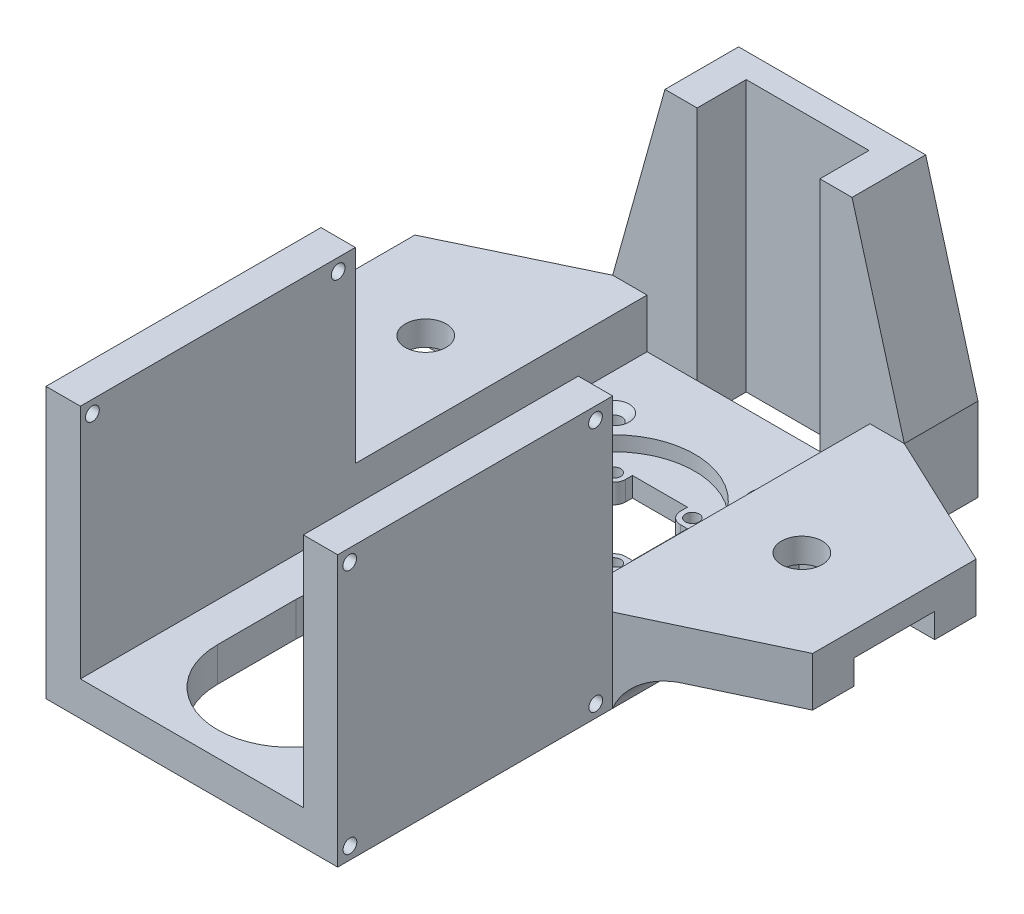
SolidWorks part; units mm, degrees
ref_plane "Front Plane" through (0, 0, 0) normal (0, 0, 1) x (1, 0, 0)
ref_plane "Top Plane" through (0, 0, 0) normal (0, 1, 0) x (1, 0, 0)
ref_plane "Right Plane" through (0, 0, 0) normal (1, 0, 0) x (0, 0, -1)
sketch "Sketch1" plane through (0, 0, 0) normal (0, 1, 0) x (1, 0, 0)
  line L1 (-29.9233, 15.7991) -> (29.4767, 15.7991)
  line L2 (-29.9233, 15.7991) -> (-29.9233, -43.6009)
  line L3 (-29.9233, -43.6009) -> (29.4767, -43.6009)
  line L4 (29.4767, 15.7991) -> (29.4767, -43.6009)
  dimension "D1" = 59.4
  dimension "D2" = 59.4
extrude "Boss-Extrude1" add sketch "Sketch1" along normal blind 7
sketch "Sketch2" plane through (0, 7, 0) normal (0, 1, 0) x (1, 0, 0)
  circle A0 centre (0, -13.9009) radius 16.5
  dimension "D1" = 33
extrude "Cut-Extrude1" cut sketch "Sketch2" against normal blind 3
sketch "Sketch4" plane through (0, 7, 0) normal (0, 1, 0) x (1, 0, 0)
  circle A1 centre (0, -13.9009) radius 16.5 construction
  circle A5 centre (-15.5, 1.5991) radius 1.65
  circle A6 centre (0, -13.9009) radius 16.5 construction
  circle A7 centre (15.5, 1.5991) radius 1.65
  circle A8 centre (15.5, -29.4009) radius 1.65
  circle A9 centre (-15.5, -29.4009) radius 1.65
  point P13 (0, -13.9009)
  point P24 (0, -13.9009)
  dimension "D4" = 15.5
  dimension "D5" = 15.5
  dimension "D6" = 3.3
  dimension "D7" = 4
extrude "Cut-Extrude2" cut sketch "Sketch4" against normal blind 7
chamfer "Chamfer1" distance 1.5 angle 45 4 edges at (-15.5, 7, 31.0509) (15.5, 7, 31.0509) (15.5, 7, 0.0509) (-15.5, 7, 0.0509)
sketch "Sketch5" plane through (0, 4, 0) normal (0, 1, 0) x (1, 0, 0)
  line L0 (-8, -8.3009) -> (-9.4, -8.3009)
  line L1 (-9.4, -8.3009) -> (-9.4, -13.9009)
  line L2 (-5.6, -5.9009) -> (-5.6, -4.5009)
  line L3 (-5.6, -4.5009) -> (0, -4.5009)
  line L4 (0, -4.5009) -> (0, -13.9009)
  line L5 (0, -13.9009) -> (-9.4, -13.9009)
  line L6 (0, -13.9009) -> (0, -4.5009)
  line L7 (9.4, -8.3009) -> (9.4, -13.9009)
  line L8 (8, -8.3009) -> (9.4, -8.3009)
  line L9 (5.6, -5.9009) -> (5.6, -4.5009)
  line L10 (5.6, -4.5009) -> (0, -4.5009)
  line L11 (9.4, -13.9009) -> (0, -13.9009)
  line L12 (0, -13.9009) -> (9.4, -13.9009)
  line L13 (5.6, -23.3009) -> (0, -23.3009)
  line L14 (5.6, -21.9009) -> (5.6, -23.3009)
  line L15 (8, -19.5009) -> (9.4, -19.5009)
  line L16 (9.4, -19.5009) -> (9.4, -13.9009)
  line L17 (0, -23.3009) -> (0, -13.9009)
  line L18 (0, -13.9009) -> (0, -23.3009)
  line L19 (-9.4, -19.5009) -> (-9.4, -13.9009)
  line L20 (-8, -19.5009) -> (-9.4, -19.5009)
  line L21 (-5.6, -21.9009) -> (-5.6, -23.3009)
  line L22 (-5.6, -23.3009) -> (0, -23.3009)
  line L23 (-9.4, -13.9009) -> (0, -13.9009)
  circle A0 centre (-8, -5.9009) radius 1.4
  circle A1 centre (0, -13.9009) radius 16.5 construction
  circle A2 centre (0, -13.9009) radius 16.5 construction
  circle A3 centre (-8, -5.9009) radius 2.4
  circle A4 centre (8, -5.9009) radius 2.4
  circle A5 centre (8, -5.9009) radius 1.4
  circle A6 centre (8, -21.9009) radius 2.4
  circle A7 centre (8, -21.9009) radius 1.4
  circle A8 centre (-8, -21.9009) radius 2.4
  circle A9 centre (-8, -21.9009) radius 1.4
  point P46 (0, -13.9009)
  dimension "D1" = 8
  dimension "D2" = 8
  dimension "D3" = 2.8
  dimension "D4" = 1
  dimension "D5" = 1.4
  dimension "D6" = 1.4
  dimension "D7" = 5.6
  dimension "D8" = 5.6
  dimension "D9" = 4
extrude "Cut-Extrude3" cut sketch "Sketch5" against normal blind 7 contours A6 L15 L16 L11 L17 L13 L14 | A8 L21 L22 L17 L5 L19 L20 | A3 L0 L1 L5 L4 L3 L2 | A4 L9 L10 L4 L11 L7 L8 | A5 | A0 | A9 | A7 region at (-4.1856, 4, 9.7153) region at (-4.1856, 4, 18.0866) region at (4.1856, 4, 9.7153) region at (4.1856, 4, 18.0866) region at (-8, 4, 5.9009) region at (8, 4, 5.9009) region at (8, 4, 21.9009) region at (-8, 4, 21.9009)
sketch "Sketch6" plane through (0, 7, 0) normal (0, 1, 0) x (1, 0, 0)
  line L0 (-29.9233, -43.6009) -> (29.4767, -43.6009) construction
  line L1 (-29.9233, 15.7991) -> (-22.9233, 15.7991)
  line L2 (-29.9233, 15.7991) -> (-29.9233, -43.6009)
  line L3 (-29.9233, -43.6009) -> (-22.9233, -43.6009)
  line L4 (-22.9233, 15.7991) -> (-22.9233, -43.6009)
  line L5 (29.4767, 15.7991) -> (-29.9233, 15.7991) construction
  line L6 (29.4767, -43.6009) -> (22.4767, -43.6009)
  line L7 (29.4767, -43.6009) -> (29.4767, 15.7991)
  line L8 (29.4767, 15.7991) -> (22.4767, 15.7991)
  line L9 (22.4767, -43.6009) -> (22.4767, 15.7991)
  dimension "D1" = 7
  dimension "D2" = 7
extrude "Boss-Extrude2" add sketch "Sketch6" along normal blind 10
sketch "Sketch7" plane through (0, 17, 0) normal (0, 1, 0) x (1, 0, 0)
  line L1 (-29.9233, 15.7991) -> (-57.15, 15.7991)
  line L2 (-29.9233, 15.7991) -> (-29.9233, -43.6009)
  line L3 (-29.9233, -43.6009) -> (-57.15, -43.6009)
  line L4 (-57.15, 15.7991) -> (-57.15, -43.6009)
  line L5 (29.4767, -43.6009) -> (57.15, -43.6009)
  line L6 (29.4767, -43.6009) -> (29.4767, 15.7991)
  line L7 (29.4767, 15.7991) -> (57.15, 15.7991)
  line L8 (57.15, -43.6009) -> (57.15, 15.7991)
  circle A0 centre (0, -13.9009) radius 16.5 construction
  dimension "D1" = 114.3
  dimension "D2" = 57.15
extrude "Boss-Extrude3" add sketch "Sketch7" against normal blind 10
sketch "Sketch8" plane through (0, 7, 0) normal (0, -1, 0) x (1, 0, 0)
  line L1 (-57.15, -15.7991) -> (-57.15, 43.6009) construction
  circle A0 centre (-38.3, 13.9009) radius 4.165
  circle A1 centre (38.3, 13.9009) radius 4.165
  dimension "D1" = 76.6
  dimension "D2" = 8.33
  dimension "D3" = 18.85
  dimension "D4" = 8.33
extrude "Cut-Extrude4" cut sketch "Sketch8" against normal blind 10
sketch "Sketch9" plane through (0, 7, 0) normal (0, -1, 0) x (1, 0, 0)
  line L0 (-29.9233, 43.6009) -> (-29.9233, -15.7991) construction
  line L1 (-59.9233, 22.1009) -> (-29.9233, 22.1009)
  line L2 (-59.9233, 22.1009) -> (-59.9233, 5.7009)
  line L3 (-59.9233, 5.7009) -> (-29.9233, 5.7009)
  line L4 (-29.9233, 22.1009) -> (-29.9233, 5.7009)
  line L5 (29.4767, 43.6009) -> (29.4767, -15.7991) construction
  line L6 (29.4767, 22.1009) -> (65.8683, 22.1009)
  line L7 (29.4767, 22.1009) -> (29.4767, 5.7009)
  line L8 (29.4767, 5.7009) -> (65.8683, 5.7009)
  line L9 (65.8683, 22.1009) -> (65.8683, 5.7009)
  circle A0 centre (-38.3, 13.9009) radius 4.165 construction
  dimension "D1" = 16.4
  dimension "D2" = 30
  dimension "D3" = 0
  dimension "D4" = 8.2
extrude "Cut-Extrude5" cut sketch "Sketch9" against normal blind 5
sketch "Sketch10" plane through (0, 7, 0) normal (0, -1, 0) x (1, 0, 0)
  line L0 (29.4767, 43.6009) -> (57.15, 30.5509)
  line L1 (57.15, 43.6009) -> (57.15, 22.1009) construction
  line L2 (57.15, 30.5509) -> (76.6251, 37.4902)
  line L3 (76.6251, 37.4902) -> (62.9409, 60.152)
  line L4 (62.9409, 60.152) -> (29.4767, 43.6009)
  line L5 (29.4767, -15.7991) -> (57.15, -2.7491)
  line L6 (57.15, 5.7009) -> (57.15, -15.7991) construction
  line L7 (57.15, -2.7491) -> (74.3098, -17.3284)
  line L8 (74.3098, -17.3284) -> (51.4239, -33.9039)
  line L9 (51.4239, -33.9039) -> (29.4767, -15.7991)
  line L12 (-29.9233, 43.6009) -> (-57.15, 30.5509)
  line L13 (-57.15, 22.1009) -> (-57.15, 43.6009) construction
  line L14 (-57.15, 30.5509) -> (-87.322, 42.7198)
  line L15 (-87.322, 42.7198) -> (-44.4169, 63.2847)
  line L16 (-44.4169, 63.2847) -> (-29.9233, 43.6009)
  line L17 (-29.9233, -15.7991) -> (-57.15, -2.7491)
  line L18 (-57.15, -15.7991) -> (-57.15, 5.7009) construction
  line L19 (-57.15, -2.7491) -> (-80.4324, -17.3313)
  line L20 (-80.4324, -17.3313) -> (-52.6315, -33.8276)
  line L21 (-52.6315, -33.8276) -> (-29.9233, -15.7991)
  circle A0 centre (38.3, 13.9009) radius 4.165 construction
  circle A1 centre (-38.3, 13.9009) radius 4.165 construction
  dimension "D1" = 33.3
  dimension "D2" = 16.65
  dimension "D3" = 33.3
  dimension "D4" = 16.65
extrude "Cut-Extrude6" cut sketch "Sketch10" against normal blind 10
sketch "Sketch11" plane through (0, 0, -15.7991) normal (0, 0, -1) x (-1, 0, 0)
  line L0 (-57.15, 17) -> (-29.4767, 17) construction
  line L1 (-29.4767, 0) -> (29.9233, 0)
  line L2 (-29.4767, 0) -> (-29.4767, 55.1)
  line L3 (-29.4767, 55.1) -> (29.9233, 55.1)
  line L4 (29.9233, 0) -> (29.9233, 55.1)
  line L5 (-29.4767, 17) -> (-18.8267, 55.1)
  line L6 (29.9233, 17) -> (19.2733, 55.1)
  line M3 (-22.4767, 17) -> (-29.4767, 17)
  line M4 (-29.4767, 17) -> (-29.4767, 7)
  line M5 (-29.4767, 7) -> (-29.4767, 0)
  line M6 (-29.4767, 0) -> (29.9233, 0)
  line M7 (29.9233, 0) -> (29.9233, 7)
  line M8 (29.9233, 7) -> (29.9233, 17)
  line M9 (29.9233, 17) -> (22.9233, 17)
  line M11 (22.9233, 17) -> (22.9233, 7)
  line M12 (22.9233, 7) -> (-22.4767, 7)
  line M13 (-22.4767, 7) -> (-22.4767, 17)
  dimension "D1" = 38.1
  dimension "D2" = 38.1
  dimension "D3" = 10.65
extrude "Boss-Extrude4" add sketch "Sketch11" along normal blind 15 contours L6 L3 L5 M9 M3 M13 M12 M11 | M3 M4 M5 M6 M7 M8 M9 M11 M12 M13 region at (-0.2233, 5.6411, -15.7991) region at (-0.2233, 30.2114, -15.7991)
sketch "Sketch12" plane through (0, 55.1, 0) normal (0, 1, 0) x (1, 0, 0)
  line L0 (18.8267, 15.7991) -> (-19.2733, 15.7991) construction
  line L1 (-12.7233, 15.7991) -> (12.2767, 15.7991)
  line L2 (-12.7233, 15.7991) -> (-12.7233, 25.7991)
  line L3 (-12.7233, 25.7991) -> (12.2767, 25.7991)
  line L4 (12.2767, 15.7991) -> (12.2767, 25.7991)
  line L6 (-19.2733, 30.7991) -> (-19.2733, 15.7991) construction
  dimension "D1" = 25
  dimension "D2" = 6.55
  dimension "D3" = 10
extrude "Cut-Extrude7" cut sketch "Sketch12" against normal blind 90
sketch "Sketch13" plane through (0, 0, 0) normal (0, -1, 0) x (1, 0, 0)
  line L0 (29.4767, -30.7991) -> (-29.9233, -30.7991) construction
  line L1 (-3.3672, -50.3659) -> (-29.9233, -30.7991)
  line L2 (-29.9233, -30.7991) -> (29.4767, -30.7991)
  line L3 (29.4767, -30.7991) -> (2.9206, -50.3659)
  circle A0 centre (-0.2233, -46.0991) radius 5.3
  circle A1 centre (-0.2233, -46.0991) radius 3.3
  line M10 (-29.9233, -30.7991) -> (29.4767, -30.7991)
  dimension "D1" = 10.6
  dimension "D2" = 15.3
  dimension "D3" = 6.6
extrude "Boss-Extrude5" add sketch "Sketch13" against normal blind 10 contours A0 L3 L1 M10 | A0 A1 region at (-0.2233, 0, -36.7597) region at (-2.546, 0, -41.5025)
sketch "Sketch14" plane through (0, 0, -30.7991) normal (0, 0, -1) x (-1, 0, 0)
  line L2 (-29.4767, 17) -> (-29.4767, 10) construction
  line L3 (29.9233, 10) -> (-29.4767, 10) construction
  circle A0 centre (-24.7767, 12.7) radius 1.4
  circle A1 centre (25.2233, 12.7) radius 1.4
  dimension "D1" = 2.8
  dimension "D2" = 2.8
  dimension "D3" = 50
  dimension "D4" = 4.7
  dimension "D5" = 2.7
extrude "Cut-Extrude8" cut sketch "Sketch14" against normal blind 10
sketch "Sketch17" plane through (0, 0, 43.6009) normal (0, 0, 1) x (1, 0, 0)
  line L0 (-29.9233, 0) -> (29.4767, 0) construction
  line L1 (-22.9233, 7) -> (22.4767, 7)
  line L2 (-22.9233, 7) -> (-22.9233, 0)
  line L3 (-22.9233, 0) -> (22.4767, 0)
  line L4 (22.4767, 7) -> (22.4767, 0)
  line L6 (-22.9233, 0) -> (-29.9233, 0)
  line L7 (-22.9233, 0) -> (-22.9233, 55.1)
  line L8 (-22.9233, 55.1) -> (-29.9233, 55.1)
  line L9 (-29.9233, 0) -> (-29.9233, 55.1)
  line L10 (22.4767, 0) -> (29.4767, 0)
  line L11 (22.4767, 0) -> (22.4767, 55.1)
  line L12 (22.4767, 55.1) -> (29.4767, 55.1)
  line L13 (29.4767, 0) -> (29.4767, 55.1)
  line M10 (-22.9233, 17) -> (-29.9233, 17)
  line M11 (-29.9233, 17) -> (-29.9233, 7)
  line M12 (-29.9233, 7) -> (-29.9233, 0)
  line M13 (-29.9233, 0) -> (29.4767, 0)
  line M14 (29.4767, 0) -> (29.4767, 7)
  line M15 (29.4767, 7) -> (29.4767, 17)
  line M16 (29.4767, 17) -> (22.4767, 17)
  line M17 (22.4767, 17) -> (22.4767, 7)
  line M18 (22.4767, 7) -> (-22.9233, 7)
  line M19 (-22.9233, 7) -> (-22.9233, 17)
  dimension "D1" = 55.1
  dimension "D2" = 55.1
extrude "Boss-Extrude8" add sketch "Sketch17" along normal blind 56 contours L9 L7 L8 M10 | L2 M19 M10 M11 M12 M13 | L4 L2 M18 M13 | L4 M17 M13 M14 M15 M16 | L13 L12 L11 M16 region at (-0.2233, 3.5, 43.6009) region at (-26.4233, 8.5, 43.6009) region at (25.9767, 8.5, 43.6009) region at (-26.4233, 36.05, 43.6009) region at (25.9767, 36.05, 43.6009)
fillet "Fillet1" radius 10 4 edges at (29.4767, 7, -5.0491) (29.4767, 7, 32.8509) (-29.9233, 7, 32.8509) (-29.9233, 7, -5.0491)
sketch "Sketch18" plane through (29.4767, 0, 0) normal (1, 0, 0) x (0, 0, -1)
  line L0 (-99.6009, 0) -> (-99.6009, 55.1) construction
  line L1 (-99.6009, 0) -> (-43.6009, 0) construction
  circle A0 centre (-97.1009, 2.5) radius 1.4
  circle A1 centre (-72.1009, 27.55) radius 14.4008
  circle A2 centre (-97.1509, 52.55) radius 1.4
  circle A3 centre (-47.1009, 52.6) radius 1.4
  circle A4 centre (-47.0509, 2.55) radius 1.4
  point P17 (-72.1009, 27.55)
  dimension "D1" = 27.5
  dimension "D2" = 2.8
  dimension "D3" = 2.5
  dimension "D4" = 2.5
  dimension "D5" = 4
extrude "Cut-Extrude10" cut sketch "Sketch18" against normal blind 65 contours A2 | A3 | A4 | A0
sketch "Sketch19" plane through (0, 7, 0) normal (0, 1, 0) x (1, 0, 0)
  line L0 (0, -79.6009) -> (0, -63.6009) construction
  line L1 (-15, -79.6009) -> (-15, -63.6009)
  line L2 (15, -79.6009) -> (15, -63.6009)
  line L3 (22.4767, -99.6009) -> (-22.9233, -99.6009) construction
  line L4 (-22.9233, -43.6009) -> (-29.9233, -43.6009) construction
  arc A0 (-15, -79.6009) -> (15, -79.6009) centre (0, -79.6009) ccw
  arc A1 (15, -63.6009) -> (-15, -63.6009) centre (0, -63.6009) ccw
  point P3 (0, -71.6009)
  dimension "D1" = 15
  dimension "D3" = 20
  dimension "D2" = 20
extrude "Cut-Extrude12" cut sketch "Sketch19" against normal blind 10
